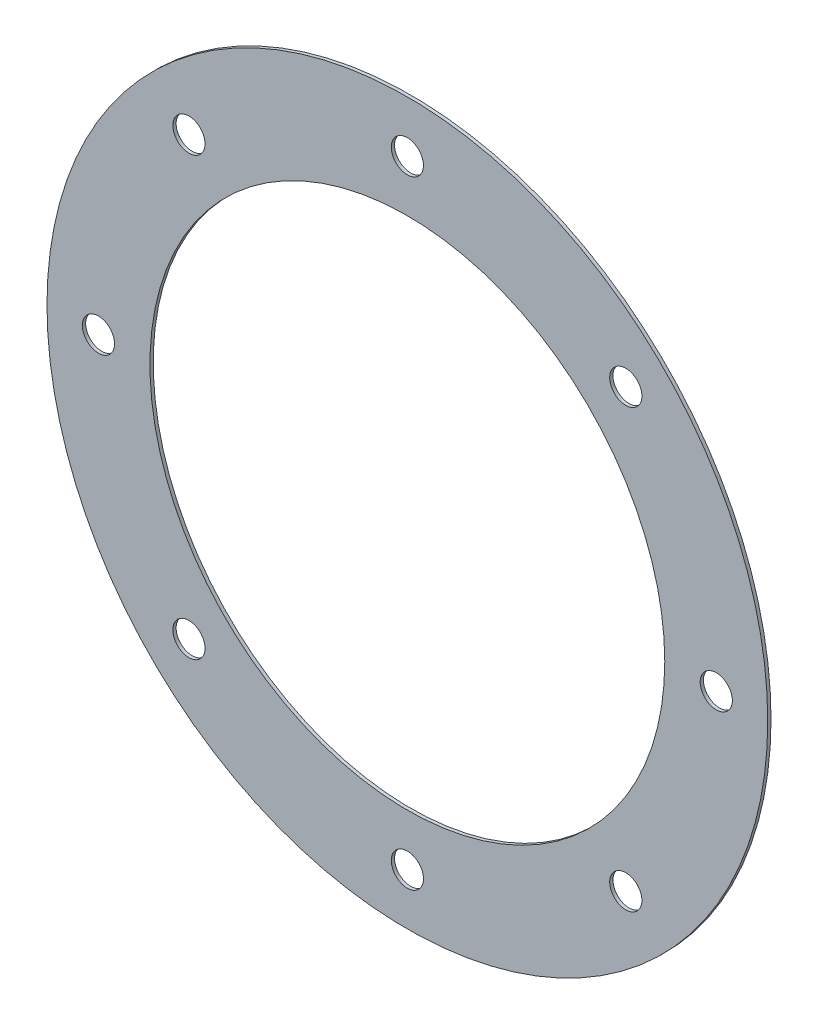
SolidWorks part; units mm, degrees
material "Wrought Stainless Steel"
ref_plane "Front Plane" through (0, 0, 0) normal (0, 0, 1) x (1, 0, 0)
ref_plane "Top Plane" through (0, 0, 0) normal (0, 1, 0) x (1, 0, 0)
ref_plane "Right Plane" through (0, 0, 0) normal (1, 0, 0) x (0, 0, -1)
sketch "Sketch1" plane through (0, 0, 0) normal (0, 0, 1) x (1, 0, 0)
  circle A0 centre (0, 0) radius 20
  circle A1 centre (0, 0) radius 28
  dimension "D1" = 40
  dimension "D2" = 56
extrude "Boss-Extrude1" add sketch "Sketch1" along normal blind 0.254
hole_wizard "Ø2.5 (2.5) Diameter Hole1" positions "Sketch3" profile "Sketch2" hole size "Ø2.5" standard "Ansi Metric"
sketch "Sketch3" plane through (0, 0, 0.254) normal (0, 0, 1) x (1, 0, 0)
  point P0 (0, 24)
  dimension "D1" = 24
sketch "Sketch2" plane through (0, 24, 0.254) normal (1, 0, 0) x (0, -1, 0)
  line L0 (0, 0) -> (0, 2.2511)
  line L1 (0, 2.2511) -> (1.25, 1.5)
  line L2 (1.25, 1.5) -> (1.25, 0)
  line L5 (1.25, 0) -> (0, 0)
  line L10 (0, 2.2511) -> (-1.25, 1.5) construction
  line L11 (0, -6.35) -> (0, 107.95) construction
  dimension "Hole Dia." = 2.5
  dimension "Hole Depth" = 1.5
  dimension "Drill Angle" = 118
ref_axis "Axis1" through (0, 0, -0.0127) along (0, 0, -1)
pattern_circular "CirPattern1" count 8 over 360 about axis through (0, 0, -0.0127) along (0, 0, -1) of "Ø2.5 (2.5) Diameter Hole1"
